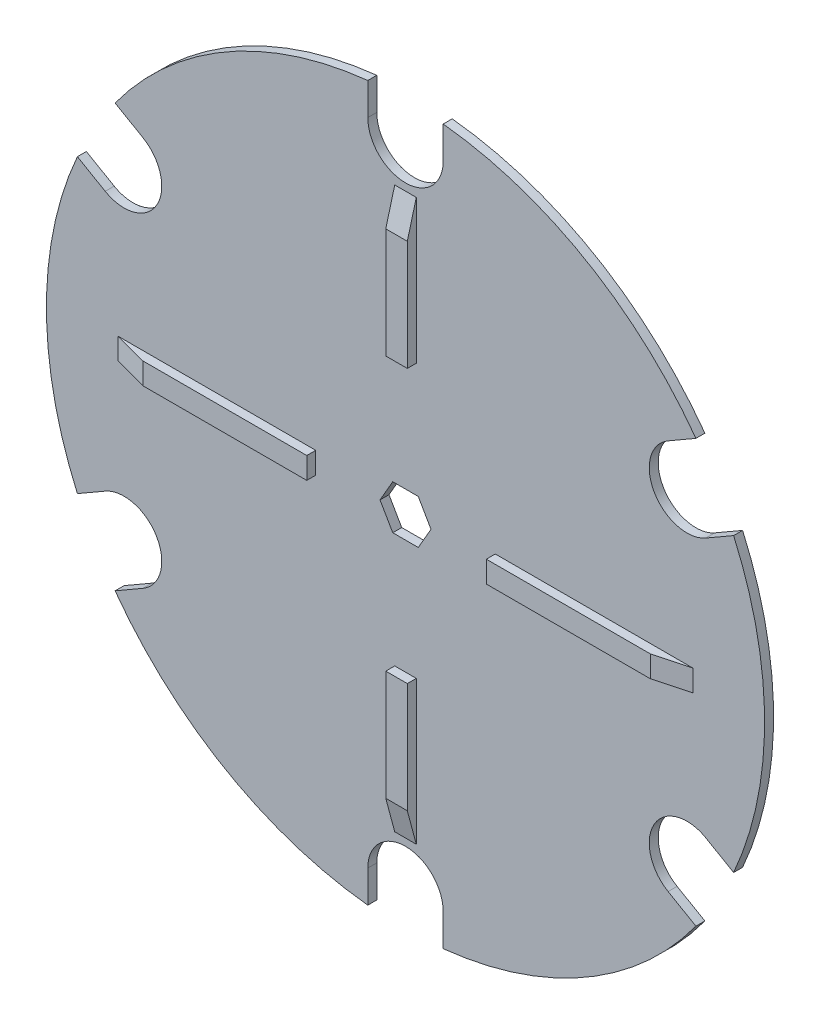
SolidWorks part; units mm, degrees
ref_plane "Front Plane" through (0, 0, 0) normal (0, 0, 1) x (1, 0, 0)
ref_plane "Top Plane" through (0, 0, 0) normal (0, 1, 0) x (1, 0, 0)
ref_plane "Right Plane" through (0, 0, 0) normal (1, 0, 0) x (0, 0, -1)
sketch "Sketch1" plane through (0, 0, 0) normal (0, 0, 1) x (1, 0, 0)
  circle A0 centre (0, 0) radius 100
extrude "Boss-Extrude1" add sketch "Sketch1" along normal blind 2.5 contours A0
sketch "Sketch8" plane through (0, 0, 0) normal (0, 0, -1) x (-1, 0, 0)
  text T0 "02-04-141118"
extrude "Cut-Extrude6" cut sketch "Sketch8" against normal blind 0.2
sketch "Sketch9" plane through (0, 0, 2.5) normal (0, 0, 1) x (1, 0, 0)
  line L1 (-7.1014, 0) -> (-3.5507, -6.15)
  line L2 (-3.5507, -6.15) -> (3.5507, -6.15)
  line L3 (3.5507, -6.15) -> (7.1014, 0)
  line L4 (7.1014, 0) -> (3.5507, 6.15)
  line L5 (3.5507, 6.15) -> (-3.5507, 6.15)
  line L6 (-3.5507, 6.15) -> (-7.1014, 0)
  circle A0 centre (0, 0) radius 6.15 construction
  dimension "D1" = 12.3
extrude "Cut-Extrude7" cut sketch "Sketch9" against normal blind 10
sketch "Sketch10" plane through (0, 0, 2.5) normal (0, 0, 1) x (1, 0, 0)
  line L2 (-10.5, -90.5) -> (-10.5, -99.4472)
  line L3 (10.5, -90.5) -> (10.5, -99.4472)
  line L4 (-10.5, -107.4101) -> (-10.5, -99.4472)
  line L5 (-10.5, -107.4101) -> (10.5, -107.4101)
  line L6 (10.5, -107.4101) -> (10.5, -99.4472)
  line L7 (-83.6253, -36.1567) -> (-91.3738, -40.6303)
  line L8 (-73.1253, -54.3433) -> (-80.8738, -58.8169)
  line L9 (-87.7699, -62.7983) -> (-80.8738, -58.8169)
  line L10 (-98.2699, -44.6118) -> (-87.7699, -62.7983)
  line L11 (-98.2699, -44.6118) -> (-91.3738, -40.6303)
  line L12 (-73.1253, 54.3433) -> (-80.8738, 58.8169)
  line L13 (-83.6253, 36.1567) -> (-91.3738, 40.6303)
  line L14 (-98.2699, 44.6118) -> (-91.3738, 40.6303)
  line L15 (-87.7699, 62.7983) -> (-98.2699, 44.6118)
  line L16 (-87.7699, 62.7983) -> (-80.8738, 58.8169)
  line L17 (10.5, 90.5) -> (10.5, 99.4472)
  line L18 (-10.5, 90.5) -> (-10.5, 99.4472)
  line L19 (-10.5, 107.4101) -> (-10.5, 99.4472)
  line L20 (10.5, 107.4101) -> (-10.5, 107.4101)
  line L21 (10.5, 107.4101) -> (10.5, 99.4472)
  line L22 (83.6253, 36.1567) -> (91.3738, 40.6303)
  line L23 (73.1253, 54.3433) -> (80.8738, 58.8169)
  line L24 (87.7699, 62.7983) -> (80.8738, 58.8169)
  line L25 (98.2699, 44.6118) -> (87.7699, 62.7983)
  line L26 (98.2699, 44.6118) -> (91.3738, 40.6303)
  line L27 (73.1253, -54.3433) -> (80.8738, -58.8169)
  line L28 (83.6253, -36.1567) -> (91.3738, -40.6303)
  line L29 (98.2699, -44.6118) -> (91.3738, -40.6303)
  line L30 (87.7699, -62.7983) -> (98.2699, -44.6118)
  line L31 (87.7699, -62.7983) -> (80.8738, -58.8169)
  arc A0 (-73.1253, -54.3433) -> (-83.6253, -36.1567) centre (-78.3753, -45.25) ccw
  arc A1 (10.5, -90.5) -> (-10.5, -90.5) centre (0, -90.5) ccw
  arc A2 (-83.6253, 36.1567) -> (-73.1253, 54.3433) centre (-78.3753, 45.25) ccw
  arc A3 (-10.5, 90.5) -> (10.5, 90.5) centre (0, 90.5) ccw
  arc A4 (73.1253, 54.3433) -> (83.6253, 36.1567) centre (78.3753, 45.25) ccw
  arc A5 (83.6253, -36.1567) -> (73.1253, -54.3433) centre (78.3753, -45.25) ccw
  point P49 (0, 0)
  dimension "D1" = 6
  dimension "D3" = 21
extrude "Cut-Extrude8" cut sketch "Sketch10" against normal blind 10
sketch "Sketch11" plane through (0, 0, 2.5) normal (0, 0, 1) x (1, 0, 0)
  line L0 (0, 0) -> (-80, 0)
  line L1 (-80, 0) -> (-80, 3)
  line L2 (-80, 3) -> (-25, 3)
  line L3 (-25, 3) -> (-25, -3)
  line L4 (-25, -3) -> (-80, -3)
  line L5 (-80, -3) -> (-80, 0)
  line L6 (0, 0) -> (0, 78)
  line L7 (0, 78) -> (-3, 78)
  line L8 (-3, 78) -> (-3, 38)
  line L9 (-3, 38) -> (3, 38)
  line L10 (3, 38) -> (3, 78)
  line L11 (3, 78) -> (0, 78)
  line L12 (25, 3) -> (80, 3)
  line L13 (25, -3) -> (25, 3)
  line L14 (80, -3) -> (25, -3)
  line L15 (80, 3) -> (80, 0)
  line L16 (80, 0) -> (80, -3)
  line L17 (3, -38) -> (-3, -38)
  line L18 (3, -78) -> (3, -38)
  line L19 (-3, -38) -> (-3, -78)
  line L20 (0, -78) -> (3, -78)
  line L21 (-3, -78) -> (0, -78)
  point P20 (0, 0)
  point P26 (0, 0)
  dimension "D1" = 3
  dimension "D2" = 6
  dimension "D3" = 6
  dimension "D4" = 3
  dimension "D5" = 80
  dimension "D6" = 55
  dimension "D7" = 78
  dimension "D8" = 40
  dimension "D9" = 2
  dimension "D10" = 2
extrude "Boss-Extrude2" add sketch "Sketch11" along normal blind 2.5 contours L7 L8 L9 L10 L11 | L1 L2 L3 L4 L5 | L14 L13 L12 L15 L16 | L19 L21 L20 L18 L17
chamfer "Chamfer1" distance 2.5 angle 75 4 edges at (80, 0, 5) (0, 78, 5) (0, -78, 5) (-80, 0, 5)
equation "\"1.5.00mm\"=3"
